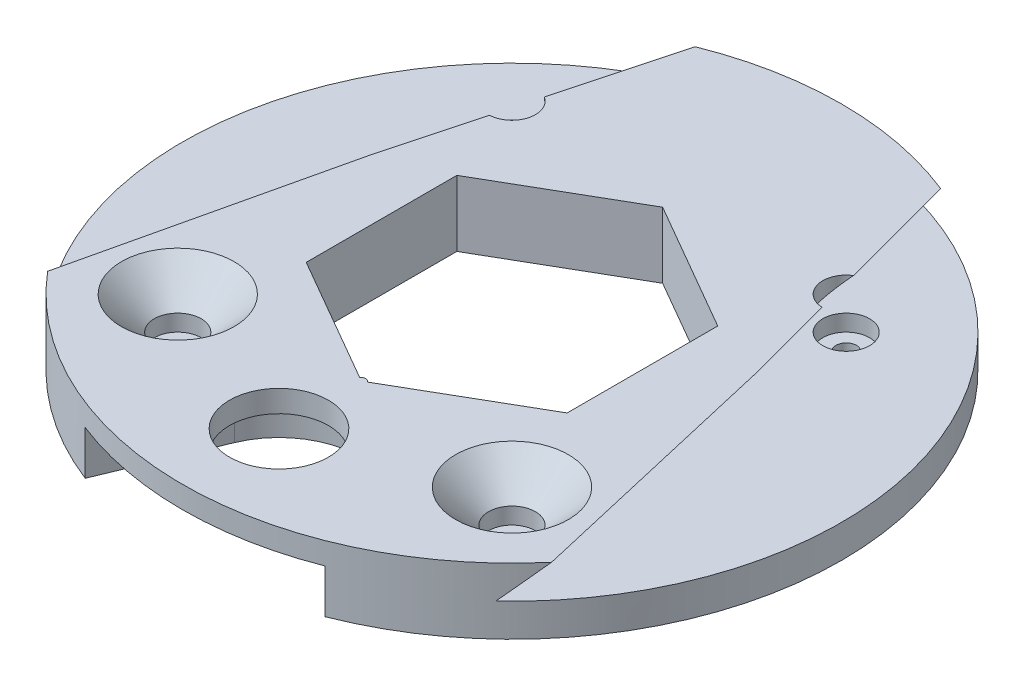
SolidWorks part; units mm, degrees
note: The reader was unsure of these and kept them because the rebuilt part matched: shared geometry of "Sketch1<6>", "Sketch5<3>".
ref_plane "Front Plane" through (0, 0, 0) normal (0, 0, 1) x (1, 0, 0)
ref_plane "Top Plane" through (0, 0, 0) normal (0, 1, 0) x (1, 0, 0)
ref_plane "Right Plane" through (0, 0, 0) normal (1, 0, 0) x (0, 0, -1)
sketch "Sketch1" plane through (0, 0, 0) normal (0, 1, 0) x (1, 0, 0)
  line L0 (-35.3553, -35.3553) -> (-12.941, 48.2963) construction
  line L1 (-34.1053, -36.5626) -> (34.1053, -36.5626) construction
  line L2 (-34.1053, -36.5626) -> (-34.1053, 36.5626) construction
  line L3 (-34.1053, 36.5626) -> (34.1053, 36.5626) construction
  line L4 (34.1053, -36.5626) -> (34.1053, 36.5626) construction
  line L5 (-34.1053, -36.5626) -> (34.1053, 36.5626) construction
  line L6 (-34.1053, 36.5626) -> (34.1053, -36.5626) construction
  line L7 (0, 96.5926) -> (0, -94.4212) construction
  line L8 (-34.1053, -36.5626) -> (-11.2548, 48.7168) construction
  line L9 (-35.3553, -35.3553) -> (35.3553, -35.3553) construction
  line L10 (-24.1481, 6.4705) -> (0, 0) construction
  line L11 (-34.1053, -36.5626) -> (-24.1481, 6.4705)
  line L12 (-24.1481, 6.4705) -> (-12.941, 48.2963)
  line L13 (34.1053, -36.5626) -> (24.1481, 6.4705)
  line L14 (24.1481, 6.4705) -> (12.941, 48.2963)
  circle A0 centre (0, 0) radius 50
  dimension "D1" = 100
  dimension "D4" = 70.7107
  dimension "D2" = 15
  dimension "D3" = 68.2107
  dimension "D5" = 15
extrude "Boss-Extrude1" add sketch "Sketch1" against normal blind 5 contours A0
extrude "Boss-Extrude3" add sketch "Sketch1<6>" along normal blind 5
sketch "Sketch1<6>" plane through (0, 0, 0) normal (0, 1, 0) x (1, 0, 0) same geometry as "Sketch1"
draft "Draft2" type of draft neutral plane draft angle 45 faces to draft 4 face at (-29.1267, 2.5, 15.0461) face at (-18.5445, 2.5, -27.3834) face at (18.5445, 2.5, -27.3834) face at (29.1267, 2.5, 15.0461) neutral plane through (0, 0, 0) neutral plane normal (0, 1, 0) reverse direction yes parameters "D1"=45
sketch "Sketch3" plane through (0, -5, 0) normal (0, -1, 0) x (1, 0, 0)
  line L1 (-35.3553, -35.3553) -> (35.3553, -35.3553) construction
  line L2 (-35.3553, -35.3553) -> (-35.3553, 35.3553) construction
  line L3 (-35.3553, 35.3553) -> (35.3553, 35.3553) construction
  line L4 (35.3553, -35.3553) -> (35.3553, 35.3553) construction
  line L5 (-35.3553, -35.3553) -> (35.3553, 35.3553) construction
  line L6 (-35.3553, 35.3553) -> (35.3553, -35.3553) construction
  circle A0 centre (0, 0) radius 50 construction
  circle A2 centre (0, 35.3553) radius 7.5
  point P0 (0, 0)
  dimension "D1" = 15
extrude "Cut-Extrude3" cut sketch "Sketch3" against normal through all both
sketch "Sketch4" plane through (0, -5, 0) normal (0, -1, 0) x (1, 0, 0)
  line L0 (0, 2.6913) -> (23.313, 58.9739)
  line L1 (-23.313, 58.9739) -> (0, 2.6913)
  line L2 (0, 25.3553) -> (0, 59.4863) construction
  circle A1 centre (0, 0) radius 50
  circle A2 centre (0, 0) radius 50
  circle A6 centre (0, 35.3553) radius 12.5
  circle A7 centre (0, 35.3553) radius 12.5
  circle M5 centre (0, 35.3553) radius 7.5
  circle M6 centre (0, 0) radius 50
  dimension "D2" = 5
  dimension "D3" = 45
  dimension "D1" = 0
extrude "Cut-Extrude5" cut sketch "Sketch4" against normal blind 6.6667 contours L2 A7 M5 | A7 L2 M5 | L2 A7 L0 M6 | A7 L2 A2 L1
sketch "Sketch5" plane through (0, -5, 0) normal (0, -1, 0) x (1, 0, 0)
  line L0 (-25.3553, 25.3553) -> (25.3553, 25.3553) construction
  line L1 (-35.3553, -35.3553) -> (35.3553, -35.3553) construction
  line L2 (-35.3553, -35.3553) -> (-35.3553, 35.3553) construction
  line L3 (-35.3553, 35.3553) -> (35.3553, 35.3553) construction
  line L4 (35.3553, -35.3553) -> (35.3553, 35.3553) construction
  line L5 (-35.3553, -35.3553) -> (35.3553, 35.3553) construction
  line L6 (-35.3553, 35.3553) -> (35.3553, -35.3553) construction
  line L7 (25.3553, -25.3553) -> (25.3553, 25.3553) construction
  line L8 (-25.3553, -25.3553) -> (25.3553, -25.3553) construction
  line L9 (-25.3553, -25.3553) -> (-25.3553, 25.3553) construction
  line L12 (0, -55) -> (0, 55) construction
  line L13 (55, 0) -> (-55, 0) construction
  arc A0 (-18.1786, 46.5783) -> (18.1786, 46.5783) centre (0, 0) ccw construction
  circle A1 centre (-25.3553, 25.3553) radius 1.55
  circle A4 centre (-25.3553, 25.3553) radius 3.55
  circle A5 centre (25.3553, 25.3553) radius 1.55
  circle A6 centre (25.3553, 25.3553) radius 3.55
  circle A7 centre (25.3553, -25.3553) radius 1.55
  circle A8 centre (25.3553, -25.3553) radius 3.55
  circle A9 centre (-25.3553, -25.3553) radius 1.55
  circle A10 centre (-25.3553, -25.3553) radius 3.55
  point P0 (0, 0)
  dimension "D3" = 3.1
  dimension "D2" = 10
  dimension "D1" = 10
  dimension "D4" = 2
extrude "Cut-Extrude6" cut sketch "Sketch5" against normal through all contours A6 A5 | A5 | A8 A7 | A7 | A9 | A10 A9 | A4 A1 | A1
extrude "Boss-Extrude4" add sketch "Sketch5<3>" against normal blind 2.5 contours A8 A7 | A10 A9 | A6 A5 | A4 A1
sketch "Sketch5<3>" plane through (0, -5, 0) normal (0, -1, 0) x (1, 0, 0) same geometry as "Sketch5"
sketch "Sketch6" plane through (0, 5, 0) normal (0, 1, 0) x (1, 0, 0)
  line L1 (0, -22.8553) -> (19.7933, -11.4277)
  line L2 (19.7933, -11.4277) -> (19.7933, 11.4277)
  line L3 (19.7933, 11.4277) -> (0, 22.8553)
  line L4 (0, 22.8553) -> (-19.7933, 11.4277)
  line L5 (-19.7933, 11.4277) -> (-19.7933, -11.4277)
  line L6 (-19.7933, -11.4277) -> (0, -22.8553)
  arc A0 (11.5485, -30.5718) -> (-11.5485, -30.5718) centre (0, -35.3553) ccw construction
  arc A1 (11.5485, -30.5718) -> (-11.5485, -30.5718) centre (0, -35.3553) ccw
  circle A2 centre (0, 0) radius 19.7933 construction
  circle A3 centre (0, -22.8553) radius 0.6639
extrude "Cut-Extrude8" cut sketch "Sketch6" against normal through all contours A3 L1 L2 L3 L4 L5 L6
chamfer "Chamfer1" distance 5 angle 45 2 edges at (25.3553, 5, 21.8053) (-25.3553, 5, 21.8053)
